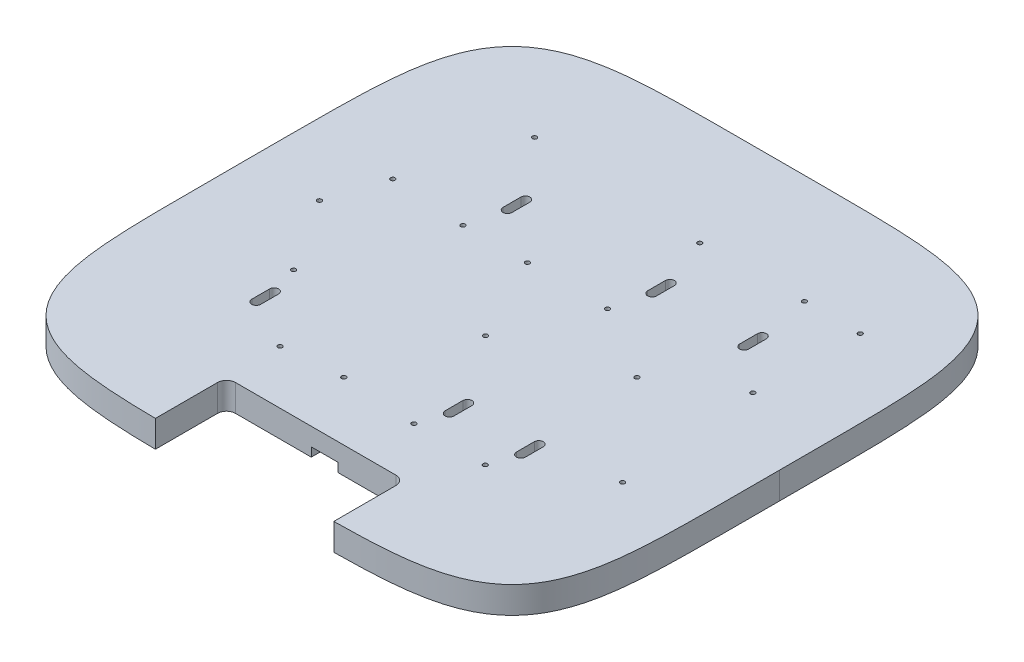
SolidWorks part; units mm, degrees
material "Сосна"
ref_plane "Спереди" through (0, 0, 0) normal (0, 0, 1) x (1, 0, 0)
ref_plane "Сверху" through (0, 0, 0) normal (0, 1, 0) x (1, 0, 0)
ref_plane "Справа" through (0, 0, 0) normal (1, 0, 0) x (0, 0, -1)
sketch "Эскиз основания" plane through (0, 0, 0) normal (0, 1, 0) x (1, 0, 0)
  line L0 (-90, -220) -> (90, -220)
  line L5 (-100, -230) -> (-100, -299.7527)
  line L7 (100, -230) -> (100, -299.7527)
  arc A6 (90, -220) -> (100, -230) centre (90, -230) cw
  arc A7 (-90, -220) -> (-100, -230) centre (-90, -230) ccw
  spline S0 degree 4 poles (300, 0) (299.9998, 8.6944) (299.9997, 21.736) (300.0012, 36.9513) (299.9906, 54.3402) (299.9623, 71.729) (299.8757, 93.4652) (299.6029, 117.242) (298.6794, 143.0506) (297.1967, 163.2872) (295.5862, 177.9573) (293.4888, 191.5009) (291.1341, 202.8581) (288.4089, 213.0451) (285.4103, 222.0487) (282.2757, 229.8814) (278.6208, 237.487) (274.4032, 244.7975) (269.5959, 251.7363) (264.1954, 258.2254) (258.2254, 264.1954) (251.7362, 269.596) (244.7974, 274.4032) (237.487, 278.6209) (229.8814, 282.2757) (222.0487, 285.4104) (213.0451, 288.4089) (202.8581, 291.1341) (191.5009, 293.4888) (177.9573, 295.5862) (163.2872, 297.1967) (143.0506, 298.6794) (117.242, 299.6029) (93.4652, 299.8758) (71.729, 299.9623) (54.3402, 299.9907) (36.9513, 300.0012) (21.736, 299.9997) (8.6944, 299.9998) (0, 300) knots 0 0 0 0 0 0.064453 0.09668 0.112793 0.128906 0.193359 0.257812 0.289062 0.320312 0.34375 0.367188 0.390625 0.40625 0.421875 0.4375 0.453125 0.46875 0.484375 0.5 0.515625 0.53125 0.546875 0.5625 0.578125 0.59375 0.609375 0.632812 0.65625 0.679688 0.710938 0.742188 0.806641 0.871094 0.887207 0.90332 0.935547 1 1 1 1 1 construction
  spline S1 degree 4 poles (300, 0) (299.9998, 8.6944) (299.9997, 21.736) (300.0012, 36.9513) (299.9906, 54.3402) (299.9623, 71.729) (299.8757, 93.4652) (299.6029, 117.242) (298.6794, 143.0506) (297.1967, 163.2872) (295.5862, 177.9573) (293.4888, 191.5009) (291.1341, 202.8581) (288.4089, 213.0451) (285.4103, 222.0487) (282.2757, 229.8814) (278.6208, 237.487) (274.4032, 244.7975) (269.5959, 251.7363) (264.1954, 258.2254) (258.2254, 264.1954) (251.7362, 269.596) (244.7974, 274.4032) (237.487, 278.6209) (229.8814, 282.2757) (222.0487, 285.4104) (213.0451, 288.4089) (202.8581, 291.1341) (191.5009, 293.4888) (177.9573, 295.5862) (163.2872, 297.1967) (143.0506, 298.6794) (117.242, 299.6029) (93.4652, 299.8758) (71.729, 299.9623) (54.3402, 299.9907) (36.9513, 300.0012) (21.736, 299.9997) (8.6944, 299.9998) (0, 300) knots 0 0 0 0 0 0.064453 0.09668 0.112793 0.128906 0.193359 0.257812 0.289062 0.320312 0.34375 0.367188 0.390625 0.40625 0.421875 0.4375 0.453125 0.46875 0.484375 0.5 0.515625 0.53125 0.546875 0.5625 0.578125 0.59375 0.609375 0.632812 0.65625 0.679688 0.710938 0.742188 0.806641 0.871094 0.887207 0.90332 0.935547 1 1 1 1 1
  spline S2 degree 4 poles (300, 0) (299.9998, -8.6944) (299.9997, -21.736) (300.0012, -36.9513) (299.9907, -54.3402) (299.9623, -71.729) (299.8758, -93.4652) (299.6029, -117.242) (298.6794, -143.0506) (297.1967, -163.2872) (295.5862, -177.9573) (293.4888, -191.5009) (291.1341, -202.8581) (288.4089, -213.0451) (285.4104, -222.0487) (282.2757, -229.8814) (278.6209, -237.487) (274.4032, -244.7975) (269.596, -251.7363) (264.1954, -258.2254) (258.2254, -264.1954) (251.7363, -269.596) (244.7975, -274.4032) (237.487, -278.6209) (229.8814, -282.2757) (222.0487, -285.4104) (213.0452, -288.4089) (202.8582, -291.1341) (191.5009, -293.4889) (177.9574, -295.5863) (163.2872, -297.1967) (143.0506, -298.6794) (117.242, -299.6029) (93.4652, -299.8758) (71.729, -299.9624) (54.3403, -299.9907) (36.9514, -300.0013) (21.7361, -299.9997) (8.6945, -299.9999) (0, -300) knots 0 0 0 0 0 0.064453 0.09668 0.112793 0.128906 0.193359 0.257812 0.289062 0.320312 0.34375 0.367188 0.390625 0.40625 0.421875 0.4375 0.453125 0.46875 0.484375 0.5 0.515625 0.53125 0.546875 0.5625 0.578125 0.59375 0.609375 0.632812 0.65625 0.679688 0.710938 0.742188 0.806641 0.871094 0.887207 0.90332 0.935547 1 1 1 1 1 construction
  spline S3 degree 4 poles (300, 0) (299.9998, -8.6944) (299.9997, -21.736) (300.0012, -36.9513) (299.9907, -54.3402) (299.9623, -71.729) (299.8758, -93.4652) (299.6029, -117.242) (298.6794, -143.0506) (297.1967, -163.2872) (295.5862, -177.9573) (293.4888, -191.5009) (291.1341, -202.8581) (288.4089, -213.0451) (285.4104, -222.0487) (282.2757, -229.8814) (278.6209, -237.487) (274.4032, -244.7975) (269.596, -251.7363) (264.1954, -258.2254) (258.2254, -264.1954) (251.7363, -269.596) (244.7975, -274.4032) (237.487, -278.6209) (229.8814, -282.2757) (222.0487, -285.4104) (213.0452, -288.4089) (202.8582, -291.1341) (191.5009, -293.4889) (177.9574, -295.5863) (163.2872, -297.1967) (143.0506, -298.6794) (124.8501, -299.3307) (110.8596, -299.611) (101.083, -299.7393) (100, -299.7527) knots 0 0 0 0 0 0.064453 0.09668 0.112793 0.128906 0.193359 0.257812 0.289062 0.320312 0.34375 0.367188 0.390625 0.40625 0.421875 0.4375 0.453125 0.46875 0.484375 0.5 0.515625 0.53125 0.546875 0.5625 0.578125 0.59375 0.609375 0.632812 0.65625 0.679688 0.710938 0.742188 0.806641 0.81467 0.81467 0.81467 0.81467 0.81467
  spline S4 degree 4 poles (-300, 0) (-299.9998, 8.6944) (-299.9997, 21.736) (-300.0012, 36.9513) (-299.9906, 54.3402) (-299.9623, 71.729) (-299.8757, 93.4652) (-299.6029, 117.242) (-298.6794, 143.0506) (-297.1967, 163.2872) (-295.5862, 177.9573) (-293.4888, 191.5009) (-291.1341, 202.8581) (-288.4089, 213.0451) (-285.4103, 222.0487) (-282.2757, 229.8814) (-278.6208, 237.487) (-274.4032, 244.7975) (-269.5959, 251.7363) (-264.1954, 258.2254) (-258.2254, 264.1954) (-251.7362, 269.596) (-244.7974, 274.4032) (-237.487, 278.6209) (-229.8814, 282.2757) (-222.0487, 285.4104) (-213.0451, 288.4089) (-202.8581, 291.1341) (-191.5009, 293.4888) (-177.9573, 295.5862) (-163.2872, 297.1967) (-143.0506, 298.6794) (-117.242, 299.6029) (-93.4652, 299.8758) (-71.729, 299.9623) (-54.3402, 299.9907) (-36.9513, 300.0012) (-21.736, 299.9997) (-8.6944, 299.9998) (0, 300) knots 0 0 0 0 0 0.064453 0.09668 0.112793 0.128906 0.193359 0.257812 0.289062 0.320312 0.34375 0.367188 0.390625 0.40625 0.421875 0.4375 0.453125 0.46875 0.484375 0.5 0.515625 0.53125 0.546875 0.5625 0.578125 0.59375 0.609375 0.632812 0.65625 0.679688 0.710938 0.742188 0.806641 0.871094 0.887207 0.90332 0.935547 1 1 1 1 1 construction
  spline S5 degree 4 poles (-300, 0) (-299.9998, 8.6944) (-299.9997, 21.736) (-300.0012, 36.9513) (-299.9906, 54.3402) (-299.9623, 71.729) (-299.8757, 93.4652) (-299.6029, 117.242) (-298.6794, 143.0506) (-297.1967, 163.2872) (-295.5862, 177.9573) (-293.4888, 191.5009) (-291.1341, 202.8581) (-288.4089, 213.0451) (-285.4103, 222.0487) (-282.2757, 229.8814) (-278.6208, 237.487) (-274.4032, 244.7975) (-269.5959, 251.7363) (-264.1954, 258.2254) (-258.2254, 264.1954) (-251.7362, 269.596) (-244.7974, 274.4032) (-237.487, 278.6209) (-229.8814, 282.2757) (-222.0487, 285.4104) (-213.0451, 288.4089) (-202.8581, 291.1341) (-191.5009, 293.4888) (-177.9573, 295.5862) (-163.2872, 297.1967) (-143.0506, 298.6794) (-117.242, 299.6029) (-93.4652, 299.8758) (-71.729, 299.9623) (-54.3402, 299.9907) (-36.9513, 300.0012) (-21.736, 299.9997) (-8.6944, 299.9998) (0, 300) knots 0 0 0 0 0 0.064453 0.09668 0.112793 0.128906 0.193359 0.257812 0.289062 0.320312 0.34375 0.367188 0.390625 0.40625 0.421875 0.4375 0.453125 0.46875 0.484375 0.5 0.515625 0.53125 0.546875 0.5625 0.578125 0.59375 0.609375 0.632812 0.65625 0.679688 0.710938 0.742188 0.806641 0.871094 0.887207 0.90332 0.935547 1 1 1 1 1
  spline S6 degree 4 poles (-300, 0) (-299.9998, -8.6944) (-299.9997, -21.736) (-300.0012, -36.9513) (-299.9907, -54.3402) (-299.9623, -71.729) (-299.8758, -93.4652) (-299.6029, -117.242) (-298.6794, -143.0506) (-297.1967, -163.2872) (-295.5862, -177.9573) (-293.4888, -191.5009) (-291.1341, -202.8581) (-288.4089, -213.0451) (-285.4104, -222.0487) (-282.2757, -229.8814) (-278.6209, -237.487) (-274.4032, -244.7975) (-269.596, -251.7363) (-264.1954, -258.2254) (-258.2254, -264.1954) (-251.7363, -269.596) (-244.7975, -274.4032) (-237.487, -278.6209) (-229.8814, -282.2757) (-222.0487, -285.4104) (-213.0452, -288.4089) (-202.8582, -291.1341) (-191.5009, -293.4889) (-177.9574, -295.5863) (-163.2872, -297.1967) (-143.0506, -298.6794) (-117.242, -299.6029) (-93.4652, -299.8758) (-71.729, -299.9624) (-54.3403, -299.9907) (-36.9514, -300.0013) (-21.7361, -299.9997) (-8.6945, -299.9999) (0, -300) knots 0 0 0 0 0 0.064453 0.09668 0.112793 0.128906 0.193359 0.257812 0.289062 0.320312 0.34375 0.367188 0.390625 0.40625 0.421875 0.4375 0.453125 0.46875 0.484375 0.5 0.515625 0.53125 0.546875 0.5625 0.578125 0.59375 0.609375 0.632812 0.65625 0.679688 0.710938 0.742188 0.806641 0.871094 0.887207 0.90332 0.935547 1 1 1 1 1 construction
  spline S7 degree 4 poles (-300, 0) (-299.9998, -8.6944) (-299.9997, -21.736) (-300.0012, -36.9513) (-299.9907, -54.3402) (-299.9623, -71.729) (-299.8758, -93.4652) (-299.6029, -117.242) (-298.6794, -143.0506) (-297.1967, -163.2872) (-295.5862, -177.9573) (-293.4888, -191.5009) (-291.1341, -202.8581) (-288.4089, -213.0451) (-285.4104, -222.0487) (-282.2757, -229.8814) (-278.6209, -237.487) (-274.4032, -244.7975) (-269.596, -251.7363) (-264.1954, -258.2254) (-258.2254, -264.1954) (-251.7363, -269.596) (-244.7975, -274.4032) (-237.487, -278.6209) (-229.8814, -282.2757) (-222.0487, -285.4104) (-213.0452, -288.4089) (-202.8582, -291.1341) (-191.5009, -293.4889) (-177.9574, -295.5863) (-163.2872, -297.1967) (-143.0506, -298.6794) (-124.8501, -299.3307) (-110.8596, -299.611) (-101.083, -299.7393) (-100, -299.7527) knots 0 0 0 0 0 0.064453 0.09668 0.112793 0.128906 0.193359 0.257812 0.289062 0.320312 0.34375 0.367188 0.390625 0.40625 0.421875 0.4375 0.453125 0.46875 0.484375 0.5 0.515625 0.53125 0.546875 0.5625 0.578125 0.59375 0.609375 0.632812 0.65625 0.679688 0.710938 0.742188 0.806641 0.81467 0.81467 0.81467 0.81467 0.81467
  point P15 (0, 0)
  dimension "D10" = 10
  dimension "D6" = 200
  dimension "D8" = 100
  dimension "D2" = 220
  dimension "D3" = 599.9999
extrude "Основание" add sketch "Эскиз основания" against normal blind 30
sketch "Эскиз разметки под крепёж" plane through (0, 0, 0) normal (0, 1, 0) x (1, 0, 0)
  line L0 (-372.0217, 60) -> (388.5777, 60) construction
  line L1 (-372.0217, -160) -> (374.4585, -160) construction
  line L2 (0, -364.7935) -> (0, 383.2318) construction
  circle A0 centre (-115, 60) radius 2.5
  circle A1 centre (47, 60) radius 2.5
  circle A2 centre (210, 60) radius 2.5
  circle A3 centre (-100, -160) radius 2.5
  circle A4 centre (50, -160) radius 2.5
  circle A5 centre (130, -160) radius 2.5
  circle A6 centre (-42.72, 60) radius 2.5
  circle A7 centre (-199.29, 65.75) radius 2.5
  circle A8 centre (-160.19, 185.5) radius 2.5
  circle A9 centre (34.8068, 175.55) radius 2.5
  circle A10 centre (150.2162, 177.55) radius 2.5
  circle A11 centre (212.76, 177.55) radius 2.5
  circle A12 centre (-166.6668, -78.149) radius 2.5
  circle A13 centre (-219.52, 3.7) radius 2.5
  circle A14 centre (-34.29, -154.25) radius 2.5
  circle A15 centre (4.81, -34.5) radius 2.5
  circle A16 centre (223.895, -100) radius 2.5
  circle A17 centre (130, 10) radius 2.5
  dimension "D2" = 5
  dimension "D3" = 5
  dimension "D4" = 5
  dimension "D9" = 5
  dimension "D10" = 5
  dimension "D11" = 5
  dimension "D7" = 5
  dimension "D18" = 5
  dimension "D19" = 5
  dimension "D20" = 5
  dimension "D21" = 5
  dimension "D22" = 5
  dimension "D23" = 5
  dimension "D24" = 5
  dimension "D25" = 5
  dimension "D26" = 5
  dimension "D27" = 5
  dimension "D28" = 5
  dimension "D5" = 60
  dimension "D6" = 220
  dimension "D8" = 130
  dimension "D12" = 50
  dimension "D13" = 100
  dimension "D14" = 210
  dimension "D15" = 47
  dimension "D16" = 115
  dimension "D17" = 89.72
  dimension "D29" = 84.29
  dimension "D30" = 5.75
  dimension "D31" = 125.5
  dimension "D32" = 45.19
  dimension "D33" = 12.1932
  dimension "D34" = 115.55
  dimension "D35" = 2.76
  dimension "D36" = 117.55
  dimension "D37" = 59.7838
  dimension "D38" = 84.29
  dimension "D39" = 5.75
  dimension "D40" = 125.5
  dimension "D41" = 45.19
  dimension "D42" = 81.851
  dimension "D43" = 66.6668
  dimension "D44" = 163.7
  dimension "D45" = 119.52
  dimension "D46" = 170
  dimension "D47" = 93.895
  dimension "D48" = 60
extrude "Разметка под крепёж" cut sketch "Эскиз разметки под крепёж" against normal through all
sketch "Эскиз проерзей для проводов" plane through (0, 0, 0) normal (0, 1, 0) x (1, 0, 0)
  line L0 (-105, 120) -> (-105, 100) construction
  line L1 (-100, 120) -> (-100, 100)
  line L2 (-110, 120) -> (-110, 100)
  line L3 (57, 120) -> (57, 100) construction
  line L4 (62, 120) -> (62, 100)
  line L5 (52, 120) -> (52, 100)
  line L6 (160.2162, 120) -> (160.2162, 100) construction
  line L7 (165.2162, 120) -> (165.2162, 100)
  line L8 (155.2162, 120) -> (155.2162, 100)
  line L9 (-156.6668, -110) -> (-156.6668, -130) construction
  line L10 (-151.6668, -110) -> (-151.6668, -130)
  line L11 (-161.6668, -110) -> (-161.6668, -130)
  line L12 (60, -110) -> (60, -130) construction
  line L13 (65, -110) -> (65, -130)
  line L14 (55, -110) -> (55, -130)
  line L15 (140, -110) -> (140, -130) construction
  line L16 (145, -110) -> (145, -130)
  line L17 (135, -110) -> (135, -130)
  arc A0 (-100, 120) -> (-110, 120) centre (-105, 120) ccw
  arc A1 (-110, 100) -> (-100, 100) centre (-105, 100) ccw
  circle A2 centre (150.2162, 177.55) radius 2.5 construction
  circle A3 centre (-115, 60) radius 2.5 construction
  arc A4 (62, 120) -> (52, 120) centre (57, 120) ccw
  arc A5 (52, 100) -> (62, 100) centre (57, 100) ccw
  circle A6 centre (47, 60) radius 2.5 construction
  arc A7 (165.2162, 120) -> (155.2162, 120) centre (160.2162, 120) ccw
  arc A8 (155.2162, 100) -> (165.2162, 100) centre (160.2162, 100) ccw
  arc A10 (-151.6668, -110) -> (-161.6668, -110) centre (-156.6668, -110) ccw
  arc A11 (-161.6668, -130) -> (-151.6668, -130) centre (-156.6668, -130) ccw
  arc A12 (65, -110) -> (55, -110) centre (60, -110) ccw
  arc A13 (55, -130) -> (65, -130) centre (60, -130) ccw
  arc A14 (145, -110) -> (135, -110) centre (140, -110) ccw
  arc A15 (135, -130) -> (145, -130) centre (140, -130) ccw
  circle A16 centre (-166.6668, -78.149) radius 2.5 construction
  circle A17 centre (50, -160) radius 2.5 construction
  circle A18 centre (130, -160) radius 2.5 construction
  point P2 (-105, 110)
  point P12 (57, 110)
  point P21 (160.2162, 110)
  point P28 (-156.6668, -120)
  point P35 (60, -120)
  point P42 (140, -120)
  dimension "D1" = 5
  dimension "D2" = 100
  dimension "D4" = 5
  dimension "D6" = 5
  dimension "D7" = 5
  dimension "D9" = 5
  dimension "D5" = 5
  dimension "D11" = 5
  dimension "D12" = 5
  dimension "D13" = 5
  dimension "D17" = 5
  dimension "D18" = 5
  dimension "D19" = 5
  dimension "D3" = 20
  dimension "D8" = 20
  dimension "D10" = 20
  dimension "D14" = 20
  dimension "D15" = 20
  dimension "D16" = 20
  dimension "D20" = 110
extrude "Прорезь для проводов" cut sketch "Эскиз проерзей для проводов" against normal through all
ref_plane "Плоскость кабель-канала" through (0, -30, 0) normal (0, 1, 0) x (1, 0, 0)
sketch "Эскиз кабель-канала" plane through (0, -30, 0) normal (0, 1, 0) x (1, 0, 0)
  line L0 (-110, 120) -> (-110, 100) construction
  line L1 (-105, 95) -> (70, 95)
  line L2 (-110, 100) -> (-110, 120)
  line L3 (-105, 125) -> (160.2162, 125)
  line L4 (165.2162, 100) -> (165.2162, 120)
  line L5 (165.2162, 100) -> (165.2162, 120) construction
  line L6 (145, -130) -> (145, -110) construction
  line L7 (-156.6668, -105) -> (70, -105)
  line L8 (-161.6668, -110) -> (-161.6668, -130)
  line L9 (-156.6668, -135) -> (-10, -135)
  line L10 (145, -110) -> (145, -130)
  line L11 (-161.6668, -110) -> (-161.6668, -130) construction
  line L12 (-90, -220) -> (90, -220) construction
  line L14 (75, 90) -> (75, -100)
  line L16 (105, 90) -> (105, -100)
  line L18 (-5, -140) -> (-5, -220)
  line L19 (-5, -220) -> (25, -220)
  line L20 (25, -140) -> (25, -220)
  line L21 (110, 95) -> (160.2162, 95)
  line L22 (110, -105) -> (140, -105)
  line L23 (30, -135) -> (140, -135)
  arc A0 (160.2162, 125) -> (165.2162, 120) centre (160.2162, 120) cw
  arc A1 (160.2162, 95) -> (165.2162, 100) centre (160.2162, 100) ccw
  arc A2 (-105, 95) -> (-110, 100) centre (-105, 100) cw
  arc A3 (-110, 120) -> (-105, 125) centre (-105, 120) cw
  arc A4 (140, -105) -> (145, -110) centre (140, -110) cw
  arc A5 (140, -135) -> (145, -130) centre (140, -130) ccw
  arc A6 (-161.6668, -130) -> (-156.6668, -135) centre (-156.6668, -130) ccw
  arc A7 (-156.6668, -105) -> (-161.6668, -110) centre (-156.6668, -110) ccw
  arc A8 (-10, -135) -> (-5, -140) centre (-10, -140) cw
  arc A9 (30, -135) -> (25, -140) centre (30, -140) ccw
  arc A10 (75, -100) -> (70, -105) centre (70, -100) cw
  arc A11 (110, -105) -> (105, -100) centre (110, -100) cw
  arc A12 (110, 95) -> (105, 90) centre (110, 90) ccw
  arc A13 (70, 95) -> (75, 90) centre (70, 90) cw
  point P15 (-110, 95)
  point P18 (-110, 125)
  point P29 (145, -105)
  point P32 (145, -135)
  point P57 (105, -105)
  dimension "D3" = 5
  dimension "D6" = 5
  dimension "D11" = 5
  dimension "D1" = 30
  dimension "D2" = 95
  dimension "D4" = 30
  dimension "D5" = 105
  dimension "D7" = 30
  dimension "D8" = 30
  dimension "D9" = 5
  dimension "D10" = 75
extrude "Каебель-канал" cut sketch "Эскиз кабель-канала" along normal blind 10
equation "\"box_width\"= 200мм"
equation "\"box_height\"= 80мм"
equation "\"D6@Эскиз основания\"=\"box_width\""
equation "\"drill\"= 5мм"
equation "\"D2@Эскиз разметки под крепёж\" = \"drill\""
equation "\"D3@Эскиз разметки под крепёж\" = \"drill\""
equation "\"D4@Эскиз разметки под крепёж\" = \"drill\""
equation "\"D9@Эскиз разметки под крепёж\" = \"drill\""
equation "\"D10@Эскиз разметки под крепёж\" = \"drill\""
equation "\"D11@Эскиз разметки под крепёж\" = \"drill\""
equation "\"D7@Эскиз разметки под крепёж\"=\"drill\""
equation "\"D18@Эскиз разметки под крепёж\"=\"drill\""
equation "\"D19@Эскиз разметки под крепёж\"=\"drill\""
equation "\"D20@Эскиз разметки под крепёж\"=\"drill\""
equation "\"D21@Эскиз разметки под крепёж\"=\"drill\""
equation "\"D22@Эскиз разметки под крепёж\"=\"drill\""
equation "\"D23@Эскиз разметки под крепёж\"=\"drill\""
equation "\"D24@Эскиз разметки под крепёж\"=\"drill\""
equation "\"D25@Эскиз разметки под крепёж\"=\"drill\""
equation "\"D26@Эскиз разметки под крепёж\"=\"drill\""
equation "\"D27@Эскиз разметки под крепёж\"=\"drill\""
equation "\"D28@Эскиз разметки под крепёж\"=\"drill\""
equation "\"D1@Основание\"=\"width\""
